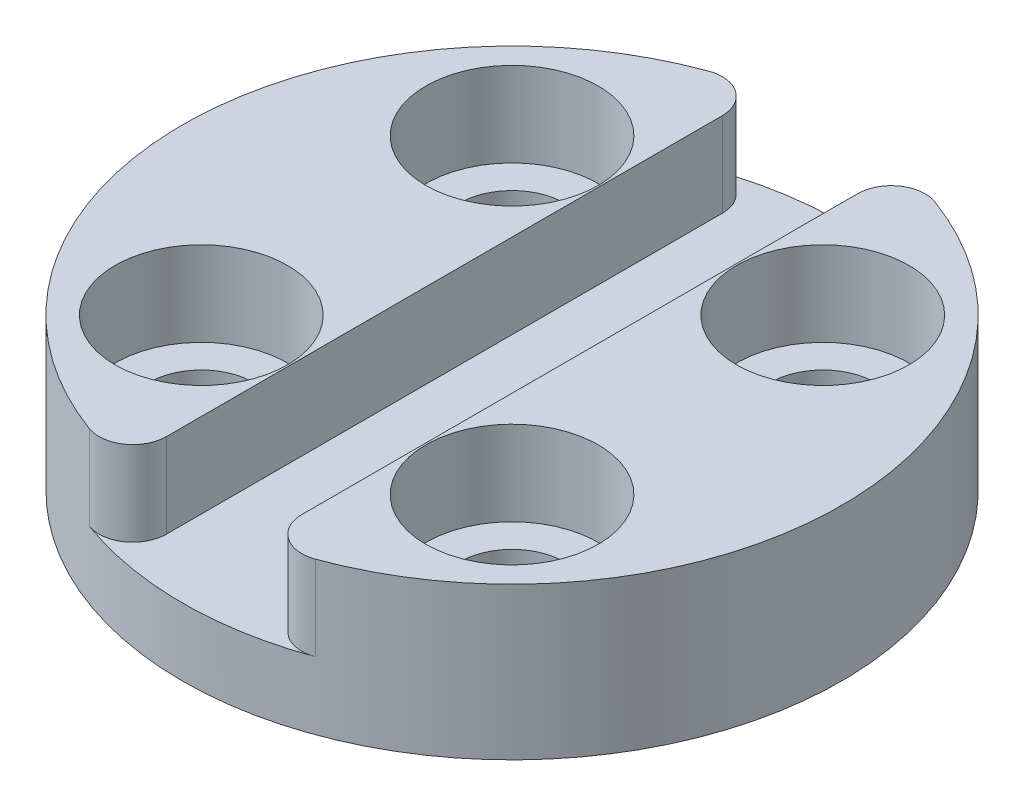
SolidWorks part; units mm, degrees
material "ABS"
ref_plane "前视基准面" through (0, 0, 0) normal (0, 0, 1) x (1, 0, 0)
ref_plane "上视基准面" through (0, 0, 0) normal (0, 1, 0) x (1, 0, 0)
ref_plane "右视基准面" through (0, 0, 0) normal (1, 0, 0) x (0, 0, -1)
sketch "草图1" plane through (0, 0, 0) normal (0, 1, 0) x (1, 0, 0)
  line L0 (0, 0) -> (8.1353, 8.1353) construction
  line L1 (0, 0) -> (0, 3.9878) construction
  circle A0 centre (0, 0) radius 9.75
  circle A1 centre (4.5962, 4.5962) radius 1.55
  circle A2 centre (4.5962, -4.5962) radius 1.55
  circle A3 centre (-4.5962, -4.5962) radius 1.55
  circle A4 centre (-4.5962, 4.5962) radius 1.55
  point P18 (0, 0)
  dimension "D1" = 19.5
  dimension "D2" = 3.1
  dimension "D3" = 6.5
  dimension "D4" = 45
  dimension "D5" = 4
extrude "凸台-拉伸1" add sketch "草图1" along normal blind 2
sketch "草图2" plane through (0, 2, 0) normal (0, 1, 0) x (1, 0, 0)
  line L0 (-2, 8.2196) -> (-2, -8.2196)
  line L1 (0, 0) -> (0, 3.7493) construction
  line L2 (2, 8.2196) -> (2, -8.2196)
  circle A0 centre (0, 0) radius 9.75 construction
  arc A1 (-3.3429, 9.159) -> (-3.3429, -9.159) centre (0, 0) ccw
  arc A2 (3.3429, -9.159) -> (3.3429, 9.159) centre (0, 0) ccw
  arc A3 (2, -8.2196) -> (3.3429, -9.159) centre (3, -8.2196) ccw
  circle A4 centre (-4.5962, 4.5962) radius 2.55
  circle A5 centre (4.5962, 4.5962) radius 2.55
  circle A6 centre (-4.5962, -4.5962) radius 2.55
  circle A7 centre (4.5962, -4.5962) radius 2.55
  arc A8 (-2, -8.2196) -> (-3.3429, -9.159) centre (-3, -8.2196) cw
  arc A9 (2, 8.2196) -> (3.3429, 9.159) centre (3, 8.2196) cw
  arc A10 (-2, 8.2196) -> (-3.3429, 9.159) centre (-3, 8.2196) ccw
  point P22 (2, -9.5427)
  point P25 (-2, -9.5427)
  point P28 (2, 9.5427)
  point P31 (-2, 9.5427)
  dimension "D1" = 5.1
  dimension "D2" = 4
  dimension "D3" = 1
extrude "凸台-拉伸2" add sketch "草图2" along normal blind 2.5
